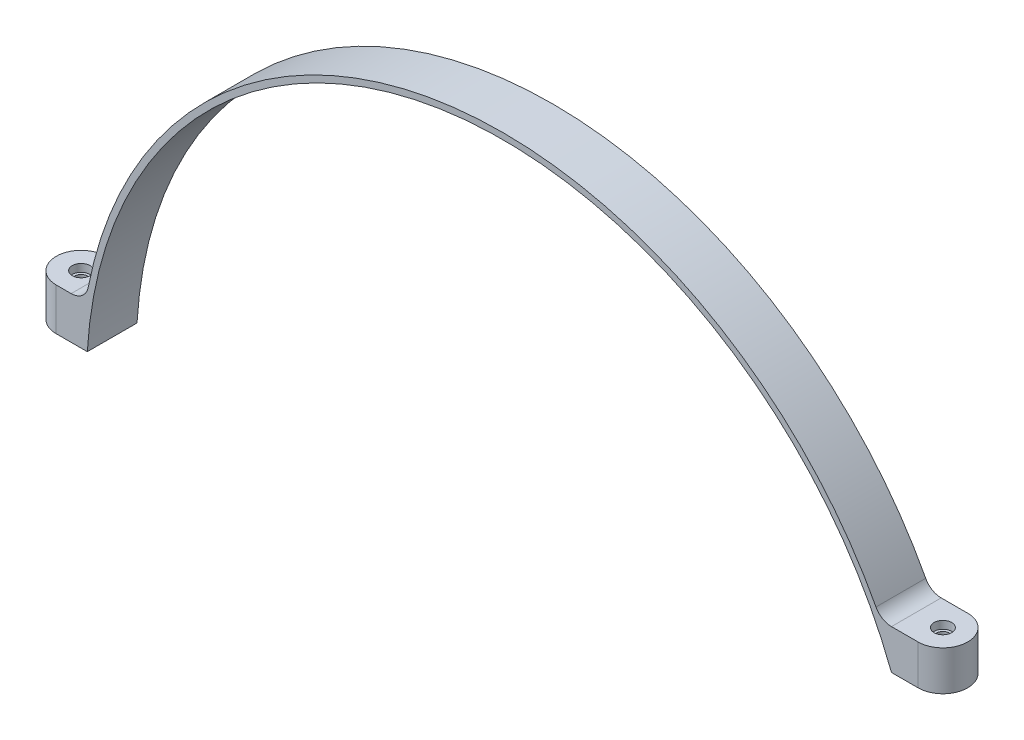
SolidWorks part; units mm, degrees
ref_plane "Plano frontal" through (0, 0, 0) normal (0, 0, 1) x (1, 0, 0)
ref_plane "Plano superior" through (0, 0, 0) normal (0, 1, 0) x (1, 0, 0)
ref_plane "Plano direito" through (0, 0, 0) normal (1, 0, 0) x (0, 0, -1)
sketch "Esboço2" plane through (0, 0, 0) normal (0, 0, 1) x (1, 0, 0)
  line L5 (157.0828, 65) -> (177.0828, 65)
  line L7 (156.3849, 60) -> (177.0828, 60)
  line L8 (177.0828, 65) -> (177.0828, 60)
  line L9 (-1000, 0) -> (49000, 0) construction
  line L10 (0, -1000) -> (0, 49000) construction
  line L12 (-189.7056, 10) -> (-167.2012, 10)
  line L17 (-189.7056, 10) -> (-189.7056, 15)
  line L18 (-189.7056, 15) -> (-169.3369, 15)
  arc A0 (157.0828, 65) -> (-169.3369, 15) centre (0, 0) ccw
  arc A1 (156.3849, 60) -> (-167.2012, 10) centre (0, 0) ccw
  dimension "D2" = 170
  dimension "D5" = 335
  dimension "D6" = 5
  dimension "D3" = 5
  dimension "D4" = 20
  dimension "D8" = 60
extrude "Ressalto-extrusão6" add sketch "Esboço2" along normal blind 20 contours A1 L12 L17 L18 A0 L5 L8 L7
fillet "Filete4" radius 10 2 edges at (177.0828, 62.5, 0) (177.0828, 62.5, 20)
fillet "Filete5" radius 10 2 edges at (-189.7056, 12.5, 0) (-189.7056, 12.5, 20)
sketch "Esboço20" plane through (0, 10, 0) normal (0, -1, 0) x (1, 0, 0)
  line L0 (-167.2012, 20) -> (-167.2012, 0)
  line L1 (-189.7056, 10) -> (-204.5078, 10) construction
  line L2 (-179.7056, 20) -> (-167.2012, 20)
  line L3 (-179.7056, 0) -> (-167.2012, 0)
  arc A0 (-189.7056, 10) -> (-179.7056, 20) centre (-179.7056, 10) cw
  arc A1 (-179.7056, 0) -> (-189.7056, 10) centre (-179.7056, 10) cw
extrude "Ressalto-extrusão14" add sketch "Esboço20" against normal blind 17
sketch "Esboço21" plane through (0, 60, 0) normal (0, -1, 0) x (1, 0, 0)
  line L0 (156.3849, 20) -> (156.3849, 0)
  line L1 (156.3849, 20) -> (167.0828, 20)
  line L2 (156.3849, 0) -> (167.0828, 0)
  arc A0 (167.0828, 20) -> (177.0828, 10) centre (167.0828, 10) cw
  arc A1 (177.0828, 10) -> (167.0828, 0) centre (167.0828, 10) cw
extrude "Ressalto-extrusão15" add sketch "Esboço21" against normal blind 16
fillet "Filete6" radius 7 1 edges at (156.3849, 66.6615, 10)
fillet "Filete7" radius 7 1 edges at (-167.8422, 27, 10)
sketch "Esboço25" plane through (0, 10, 0) normal (0, -1, 0) x (1, 0, 0)
  circle A0 centre (-179.7056, 10) radius 2.5
  dimension "D1" = 5
extrude "Corte-extrusão1" cut sketch "Esboço25" against normal blind 16
sketch "Esboço27" plane through (0, 10, 0) normal (0, -1, 0) x (1, 0, 0)
  circle A0 centre (-179.7056, 10) radius 2.5
extrude "Corte-extrusão2" cut sketch "Esboço27" against normal blind 18
sketch "Esboço28" plane through (0, 27, 0) normal (0, 1, 0) x (1, 0, 0)
  circle A0 centre (-179.7056, -10) radius 3.55
  dimension "D1" = 7.1
extrude "Corte-extrusão3" cut sketch "Esboço28" against normal blind 3.1
sketch "Esboço29" plane through (0, 60, 0) normal (0, -1, 0) x (1, 0, 0)
  circle A0 centre (167.0828, 10) radius 2.5
  dimension "D1" = 5
extrude "Corte-extrusão4" cut sketch "Esboço29" against normal blind 22.1
sketch "Esboço30" plane through (0, 76, 0) normal (0, 1, 0) x (1, 0, 0)
  circle A0 centre (167.0828, -10) radius 3.55
  dimension "D1" = 7.1
extrude "Corte-extrusão5" cut sketch "Esboço30" against normal blind 3.1
